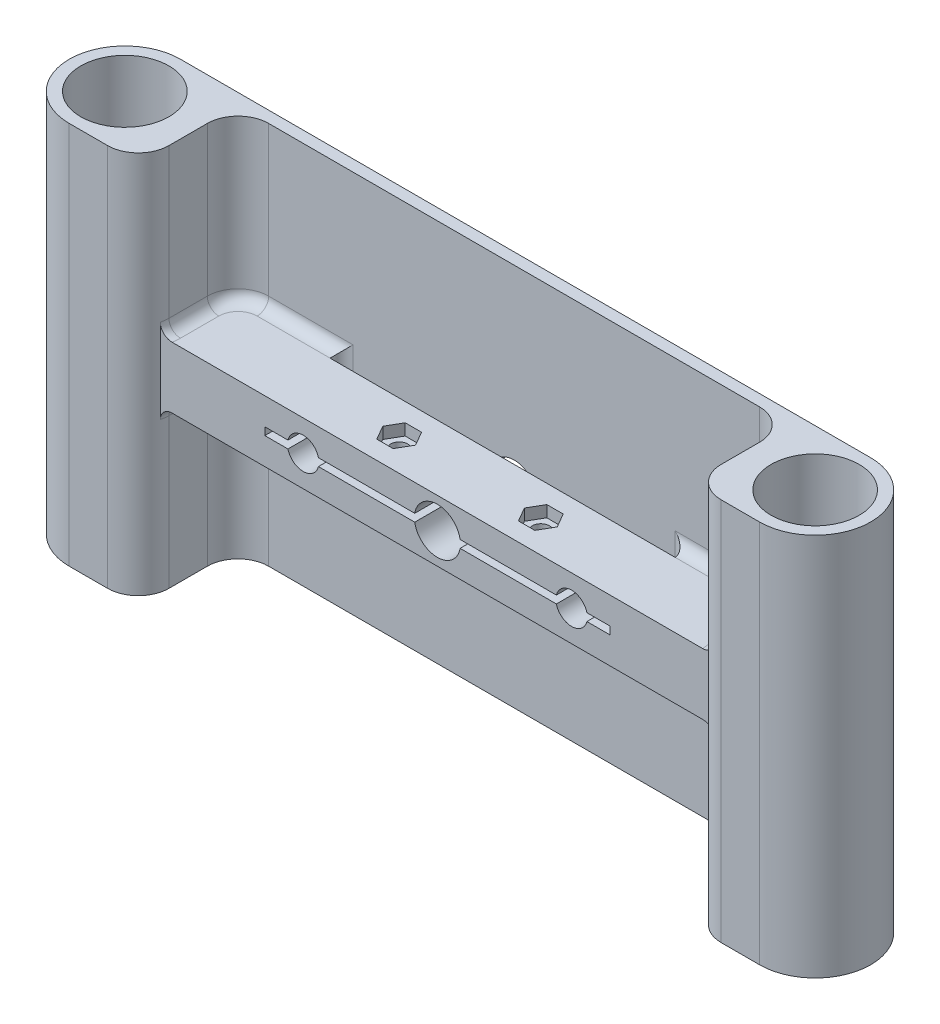
SolidWorks part; units mm, degrees
ref_plane "Front Plane" through (0, 0, 0) normal (0, 0, 1) x (1, 0, 0)
ref_plane "Top Plane" through (0, 0, 0) normal (0, 1, 0) x (1, 0, 0)
ref_plane "Right Plane" through (0, 0, 0) normal (1, 0, 0) x (0, 0, -1)
sketch "Sketch1" plane through (0, 0, 0) normal (0, 1, 0) x (1, 0, 0)
  line L0 (137.4606, -14.5) -> (119.4606, -14.5)
  line L1 (119.4606, -14.5) -> (119.4606, 11.5)
  line L2 (-42.5394, -14.5) -> (-24.5394, -14.5)
  line L3 (-42.5394, 14.5) -> (137.4606, 14.5)
  line L4 (119.4606, 11.5) -> (-24.5394, 11.5)
  line L5 (-24.5394, -14.5) -> (-24.5394, 11.5)
  circle A0 centre (-42.5394, 0) radius 11.5
  circle A1 centre (137.4606, 0) radius 11.5
  arc A2 (-42.5394, -14.5) -> (-42.5394, 14.5) centre (-42.5394, 0) cw
  arc A6 (137.4606, 14.5) -> (137.4606, -14.5) centre (137.4606, 0) cw
  dimension "D3" = 23
  dimension "D4" = 23
  dimension "D5" = 180
  dimension "D6" = 3
  dimension "D1" = 18
  dimension "D2" = 18
  dimension "D8" = 3
extrude "Boss-Extrude1" add sketch "Sketch1" along normal blind 100
fillet "Fillet1" radius 8 4 edges at (119.4606, 50, -11.5) (119.4606, 50, 14.5) (-24.5394, 50, -11.5) (-24.5394, 50, 14.5)
sketch "Sketch2" plane through (0, 0, -11.5) normal (0, 0, 1) x (1, 0, 0)
  line L0 (47.4606, 100) -> (47.4606, 0) construction
  line L1 (-16.5394, 100) -> (111.4606, 100) construction
  line L2 (-16.5394, 0) -> (111.4606, 0) construction
  circle A0 centre (12.4606, 50) radius 4.1
  circle A1 centre (82.4606, 50) radius 4.1
  circle A2 centre (47.4606, 50) radius 6
  point P10 (47.4606, 50)
  dimension "D1" = 8.2
  dimension "D2" = 8.2
  dimension "D5" = 12
  dimension "D3" = 35
  dimension "D4" = 35
extrude "Cut-Extrude1" cut sketch "Sketch2" against normal blind 10
sketch "Sketch3" plane through (0, 0, -11.5) normal (0, 0, 1) x (1, 0, 0)
  line L0 (12.4606, 58) -> (82.4606, 58)
  line L1 (12.4606, 42) -> (82.4606, 42)
  line L2 (12.4606, 58) -> (-16.5394, 58)
  line L3 (-16.5394, 100) -> (-16.5394, 0) construction
  line L4 (-16.5394, 58) -> (-28.8663, 58)
  line L5 (-28.8663, 58) -> (-28.8663, 42)
  line L6 (-28.8663, 42) -> (12.4606, 42)
  line L7 (82.4606, 58) -> (124.1494, 58)
  line L8 (124.1494, 58) -> (124.1494, 42)
  line L9 (124.1494, 42) -> (82.4606, 42)
  circle A2 centre (12.4606, 50) radius 4.1
  circle A3 centre (82.4606, 50) radius 4.1
  circle A4 centre (47.4606, 50) radius 6
  dimension "D2" = 12
extrude "Boss-Extrude2" add sketch "Sketch3" along normal blind 20
fillet "Fillet2" radius 3 14 edges at (-24.6032, 42, 7.508) (-24.5394, 42, 1.5) (-22.1963, 42, -9.1569) (119.5243, 42, 7.508) (119.4606, 42, 1.5) (117.1174, 42, -9.1569) (119.5243, 58, 7.508) (119.4606, 58, 1.5) (-24.6032, 58, 7.508) (-24.5394, 58, 1.5) (-22.1963, 58, -9.1569) (47.4606, 58, -11.5) (47.4606, 42, -11.5) (117.1174, 58, -9.1569)
sketch "Sketch4" plane through (0, 0, 8.5) normal (0, 0, 1) x (1, 0, 0)
  line L0 (47.4606, 50) -> (2.4606, 50)
  line L1 (47.4606, 50) -> (92.4606, 50)
  dimension "D1" = 45
extrude "Cut-Extrude-Thin1" cut sketch "Sketch4" against normal up to surface (20 mm away) and the other way through all thin up to face at (47.4606, 19.5, -11.5) thin type mid plane wall 2
sketch "Sketch5" plane through (0, 42, 0) normal (0, -1, 0) x (-1, 0, 0)
  line L0 (-2.4606, 8.5) -> (-47.4606, 8.5)
  line L1 (16.5394, 8.5) -> (-111.4606, 8.5) construction
  line L2 (-47.4606, 8.5) -> (-92.4606, 8.5)
  dimension "D1" = 45
  dimension "D2" = 45
extrude "Cut-Extrude-Thin2" cut sketch "Sketch5" against normal blind 20 and the other way through all thin thin type one direction wall 3
fillet "Fillet3" radius 3 2 edges at (92.4606, 50, -11.5) (2.4606, 50, -11.5)
sketch "Sketch6" plane through (0, 49, 0) normal (0, 1, 0) x (1, 0, 0)
  line L0 (16.4368, 8.5) -> (41.5445, -8.5) construction
  line L1 (41.5445, -8.5) -> (53.3767, -8.5) construction
  line L2 (53.3767, -8.5) -> (78.4844, 8.5) construction
  circle A0 centre (28.9906, 0) radius 2.25
  circle A1 centre (65.9305, 0) radius 2.25
  dimension "D1" = 4.5
  dimension "D2" = 4.5
extrude "Cut-Extrude2" cut sketch "Sketch6" against normal through all both and the other way through all
sketch "Sketch7" plane through (0, 58, 0) normal (0, 1, 0) x (1, 0, 0)
  line L1 (33.263, 0) -> (31.1268, 3.7)
  line L2 (31.1268, 3.7) -> (26.8544, 3.7)
  line L3 (26.8544, 3.7) -> (24.7182, 0)
  line L4 (24.7182, 0) -> (26.8544, -3.7)
  line L5 (26.8544, -3.7) -> (31.1268, -3.7)
  line L6 (31.1268, -3.7) -> (33.263, 0)
  line L7 (70.2029, 0) -> (68.0667, 3.7)
  line L8 (68.0667, 3.7) -> (63.7943, 3.7)
  line L9 (63.7943, 3.7) -> (61.6581, 0)
  line L10 (61.6581, 0) -> (63.7943, -3.7)
  line L11 (63.7943, -3.7) -> (68.0667, -3.7)
  line L12 (68.0667, -3.7) -> (70.2029, 0)
  circle A0 centre (28.9906, 0) radius 3.7 construction
  circle A1 centre (65.9305, 0) radius 3.7 construction
  dimension "D1" = 7.4
  dimension "D2" = 7.4
extrude "Cut-Extrude3" cut sketch "Sketch7" against normal blind 3
